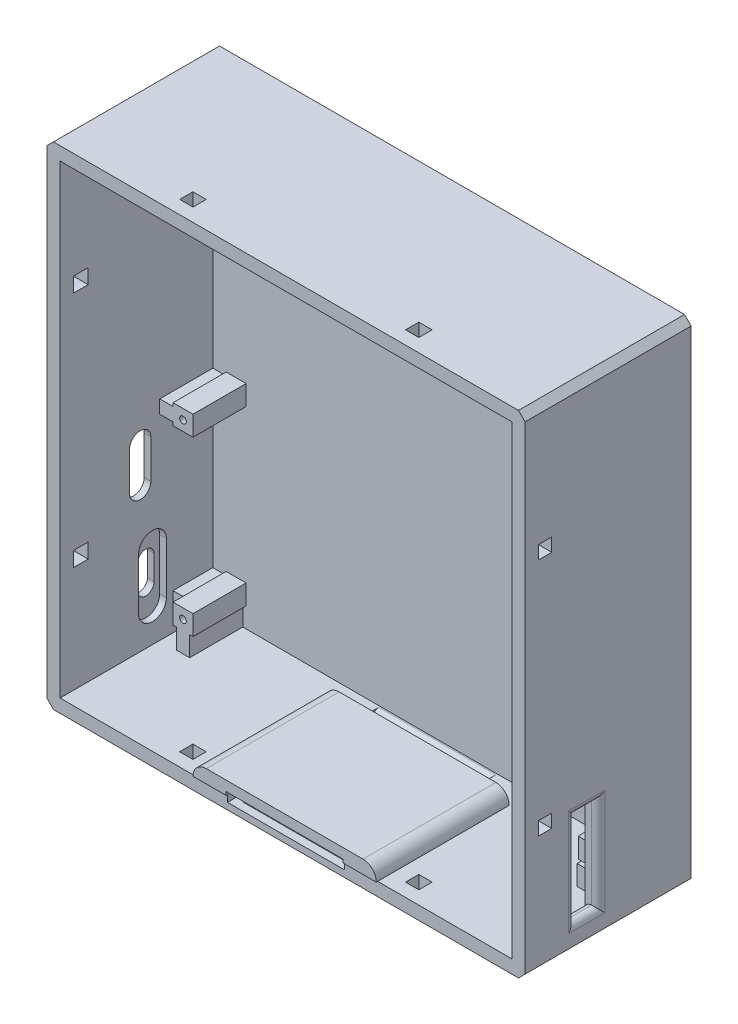
SolidWorks part; units mm, degrees
ref_plane "前视基准面" through (0, 0, 0) normal (0, 0, 1) x (1, 0, 0)
ref_plane "上视基准面" through (0, 0, 0) normal (0, 1, 0) x (1, 0, 0)
ref_plane "右视基准面" through (0, 0, 0) normal (1, 0, 0) x (0, 0, -1)
sketch "草图1" plane through (0, 0, 0) normal (0, 0, 1) x (1, 0, 0)
  line L1 (-21.8087, 48.178) -> (50.1913, 48.178)
  line L2 (-21.8087, 48.178) -> (-21.8087, -25.822)
  line L3 (-21.8087, -25.822) -> (50.1913, -25.822)
  line L4 (50.1913, 48.178) -> (50.1913, -25.822)
  dimension "D1" = 74
  dimension "D2" = 72
extrude "凸台-拉伸1" add sketch "草图1" along normal blind 25
sketch "草图2" plane through (0, 0, 25) normal (0, 0, 1) x (1, 0, 0)
  line L0 (50.1913, 48.178) -> (-21.8087, 48.178) construction
  line L1 (-19.8087, 46.178) -> (48.1913, 46.178)
  line L2 (-19.8087, 46.178) -> (-19.8087, -23.822)
  line L3 (-19.8087, -23.822) -> (48.1913, -23.822)
  line L4 (48.1913, 46.178) -> (48.1913, -23.822)
  line L5 (-21.8087, -25.822) -> (50.1913, -25.822) construction
  line L6 (50.1913, -25.822) -> (50.1913, 48.178) construction
  line L7 (-21.8087, 48.178) -> (-21.8087, -25.822) construction
  dimension "D1" = 2
  dimension "D2" = 2
  dimension "D3" = 2
  dimension "D4" = 2
extrude "切除-拉伸1" cut sketch "草图2" against normal blind 23
sketch "草图3" plane through (0, 46.178, 0) normal (0, -1, 0) x (1, 0, 0)
  line L0 (48.1913, 25) -> (-19.8087, 25) construction
  line L1 (-3.8087, 23) -> (-1.8087, 23)
  line L2 (-3.8087, 23) -> (-3.8087, 21)
  line L3 (-3.8087, 21) -> (-1.8087, 21)
  line L4 (-1.8087, 23) -> (-1.8087, 21)
  line L5 (30.1913, 23) -> (32.1913, 23)
  line L6 (30.1913, 23) -> (30.1913, 21)
  line L7 (30.1913, 21) -> (32.1913, 21)
  line L8 (32.1913, 23) -> (32.1913, 21)
  line L9 (48.1913, 2) -> (48.1913, 25) construction
  line L10 (-19.8087, 2) -> (-19.8087, 25) construction
  dimension "D1" = 2
  dimension "D2" = 2
  dimension "D3" = 2
  dimension "D4" = 16
  dimension "D5" = 16
extrude "切除-拉伸2" cut sketch "草图3" against normal up to next
sketch "草图4" plane through (48.1913, 0, 0) normal (-1, 0, 0) x (0, 0, 1)
  line L1 (23, 30.178) -> (21, 30.178)
  line L2 (23, 30.178) -> (23, 28.178)
  line L3 (23, 28.178) -> (21, 28.178)
  line L4 (21, 30.178) -> (21, 28.178)
  line L5 (23, -5.822) -> (21, -5.822)
  line L6 (23, -5.822) -> (23, -7.822)
  line L7 (23, -7.822) -> (21, -7.822)
  line L8 (21, -5.822) -> (21, -7.822)
  line L10 (25, -23.822) -> (25, 46.178) construction
  line L11 (2, 46.178) -> (25, 46.178) construction
  line L12 (2, -23.822) -> (25, -23.822) construction
  dimension "D1" = 2
  dimension "D2" = 2
  dimension "D3" = 2
  dimension "D4" = 16
  dimension "D5" = 16
sketch "草图5" plane through (0, -23.822, 0) normal (0, 1, 0) x (1, 0, 0)
  line L0 (-19.8087, -25) -> (48.1913, -25) construction
  line L1 (32.1913, -23) -> (30.1913, -23)
  line L2 (32.1913, -23) -> (32.1913, -21)
  line L3 (32.1913, -21) -> (30.1913, -21)
  line L4 (30.1913, -23) -> (30.1913, -21)
  line L5 (-1.8087, -23) -> (-3.8087, -23)
  line L6 (-1.8087, -23) -> (-1.8087, -21)
  line L7 (-1.8087, -21) -> (-3.8087, -21)
  line L8 (-3.8087, -23) -> (-3.8087, -21)
  line L9 (48.1913, -2) -> (48.1913, -25) construction
  line L10 (-19.8087, -2) -> (-19.8087, -25) construction
  dimension "D1" = 2
  dimension "D2" = 2
  dimension "D3" = 16
  dimension "D4" = 16
sketch "草图6" plane through (-19.8087, 0, 0) normal (1, 0, 0) x (0, 0, -1)
  line L0 (-25, 46.178) -> (-25, -23.822) construction
  line L1 (-23, 30.178) -> (-20.7747, 30.178)
  line L2 (-23, 30.178) -> (-23, 27.9527)
  line L3 (-23, 27.9527) -> (-20.7747, 27.9527)
  line L4 (-20.7747, 30.178) -> (-20.7747, 27.9527)
  line L5 (-23, -5.5967) -> (-20.7747, -5.5967)
  line L6 (-23, -5.5967) -> (-23, -7.822)
  line L7 (-23, -7.822) -> (-20.7747, -7.822)
  line L8 (-20.7747, -5.5967) -> (-20.7747, -7.822)
  line L9 (-2, -23.822) -> (-25, -23.822) construction
  line L10 (-2, 46.178) -> (-25, 46.178) construction
  dimension "D1" = 2
  dimension "D2" = 16
  dimension "D3" = 16
extrude "切除-拉伸3" cut sketch "草图4" against normal up to next
extrude "切除-拉伸4" cut sketch "草图5" against normal up to next
extrude "切除-拉伸5" cut sketch "草图6" against normal up to next
sketch "草图7" plane through (0, 0, 2) normal (0, 0, 1) x (1, 0, 0)
  line L1 (-17.8087, -20.822) -> (-14.8087, -20.822)
  line L2 (-17.8087, -20.822) -> (-17.8087, -17.822)
  line L3 (-17.8087, -17.822) -> (-14.8087, -17.822)
  line L4 (-14.8087, -20.822) -> (-14.8087, -17.822)
  line L5 (-17.8087, 5.178) -> (-14.8087, 5.178)
  line L6 (-17.8087, 5.178) -> (-17.8087, 8.178)
  line L7 (-17.8087, 8.178) -> (-14.8087, 8.178)
  line L8 (-14.8087, 5.178) -> (-14.8087, 8.178)
  line L9 (43.1913, -20.822) -> (46.1913, -20.822)
  line L10 (43.1913, -20.822) -> (43.1913, -17.822)
  line L11 (43.1913, -17.822) -> (46.1913, -17.822)
  line L12 (46.1913, -20.822) -> (46.1913, -17.822)
  line L13 (43.1913, 5.178) -> (46.1913, 5.178)
  line L14 (43.1913, 5.178) -> (43.1913, 8.178)
  line L15 (43.1913, 8.178) -> (46.1913, 8.178)
  line L16 (46.1913, 5.178) -> (46.1913, 8.178)
  line L18 (48.1913, -23.822) -> (48.1913, 46.178) construction
  line L19 (-19.8087, 46.178) -> (-19.8087, -23.822) construction
  line L20 (-19.8087, -23.822) -> (48.1913, -23.822) construction
  dimension "D1" = 3
  dimension "D2" = 23
  dimension "D3" = 2
  dimension "D4" = 3
  dimension "D5" = 2
extrude "凸台-拉伸2" add sketch "草图7" along normal blind 8
sketch "草图10" plane through (0, 0, 10) normal (0, 0, 1) x (1, 0, 0)
  line L0 (-17.8087, -17.822) -> (-14.8087, -20.822) construction
  line L1 (-14.8087, -20.822) -> (-14.8087, -17.822) construction
  line L2 (-14.8087, -17.822) -> (-17.8087, -20.822) construction
  line L3 (43.1913, 8.178) -> (46.1913, 5.178) construction
  line L4 (46.1913, 5.178) -> (46.1913, 8.178) construction
  line L5 (46.1913, 8.178) -> (43.1913, 5.178) construction
  circle A0 centre (44.6913, 6.678) radius 0.5
  circle A1 centre (44.6913, -19.322) radius 0.5
  circle A2 centre (-16.3087, -19.322) radius 0.5
  circle A3 centre (-16.3087, 6.678) radius 0.5
  point P17 (-16.3087, -19.322)
  point P26 (44.6913, 6.678)
  dimension "D1" = 1
extrude "切除-拉伸6" cut sketch "草图10" against normal blind 3
sketch "草图12" plane through (-17.8087, 0, 0) normal (-1, 0, 0) x (0, 0, 1)
  line L1 (2, -18.322) -> (8, -18.322)
  line L2 (2, -18.322) -> (2, -20.322)
  line L3 (2, -20.322) -> (8, -20.322)
  line L4 (8, -18.322) -> (8, -20.322)
  line L5 (2, -17.822) -> (2, -20.822) construction
  line L6 (10, -17.822) -> (10, -20.822) construction
  line L7 (2, 7.678) -> (10, 7.678)
  line L8 (2, 7.678) -> (2, 5.678)
  line L9 (2, 5.678) -> (10, 5.678)
  line L10 (10, 7.678) -> (10, 5.678)
  line L11 (10, 5.178) -> (2, 5.178) construction
  line L12 (10, 8.178) -> (10, 5.178) construction
  line L13 (2, 8.178) -> (2, 5.178) construction
  line L14 (10, -20.822) -> (2, -20.822) construction
  dimension "D1" = 0.5
  dimension "D2" = 2
  dimension "D3" = 2
  dimension "D4" = 0.5
  dimension "D5" = 2
extrude "凸台-拉伸3" add sketch "草图12" along normal up to next
sketch "草图13" plane through (46.1913, 0, 0) normal (1, 0, 0) x (0, 0, -1)
  line L1 (-10, 7.678) -> (-2, 7.678)
  line L2 (-10, 7.678) -> (-10, 5.678)
  line L3 (-10, 5.678) -> (-2, 5.678)
  line L4 (-2, 7.678) -> (-2, 5.678)
  line L5 (-10, 5.178) -> (-10, 8.178) construction
  line L6 (-2, 5.178) -> (-2, 8.178) construction
  line L7 (-10, 5.178) -> (-2, 5.178) construction
  line L8 (-10, -20.822) -> (-10, -17.822) construction
  line L9 (-10, -18.322) -> (-2, -18.322)
  line L10 (-10, -18.322) -> (-10, -20.322)
  line L11 (-10, -20.322) -> (-2, -20.322)
  line L12 (-2, -18.322) -> (-2, -20.322)
  line L13 (-2, -20.822) -> (-2, -17.822) construction
  line L14 (-10, -20.822) -> (-2, -20.822) construction
  point P20 (-6, -20.822)
  dimension "D1" = 2
  dimension "D2" = 0.5
  dimension "D3" = 2
  dimension "D4" = 0.5
extrude "凸台-拉伸4" add sketch "草图13" along normal up to next
sketch "草图14" plane through (0, -20.822, 0) normal (0, -1, 0) x (1, 0, 0)
  line L0 (-17.8087, 10) -> (-14.8087, 10) construction
  line L1 (-17.3087, 10) -> (-15.3087, 10)
  line L2 (-17.3087, 10) -> (-17.3087, 2)
  line L3 (-17.3087, 2) -> (-15.3087, 2)
  line L4 (-15.3087, 10) -> (-15.3087, 2)
  line L5 (43.6913, 10.6583) -> (45.6913, 10.6583)
  line L6 (43.6913, 10.6583) -> (43.6913, 4.0576)
  line L7 (43.6913, 4.0576) -> (45.6913, 4.0576)
  line L8 (45.6913, 10.6583) -> (45.6913, 4.0576)
  line L9 (-17.8087, 2) -> (-14.8087, 2) construction
  line L11 (-17.8087, 10) -> (-17.8087, 2) construction
  line L13 (43.1913, 10) -> (43.1913, 2) construction
  dimension "D1" = 2
  dimension "D2" = 2
  dimension "D3" = 0.5
  dimension "D4" = 0.5
extrude "凸台-拉伸5" add sketch "草图14" along normal up to next
sketch "草图15" plane through (-21.8087, 0, 0) normal (-1, 0, 0) x (0, 0, 1)
  line L0 (12.94, 3.798) -> (12.94, -2.402) construction
  line L1 (16.54, 3.798) -> (16.54, -2.402)
  line L2 (9.34, 3.798) -> (9.34, -2.402)
  line L4 (25, -25.822) -> (0, -25.822) construction
  line L5 (0, 48.178) -> (0, -25.822) construction
  arc A0 (16.54, 3.798) -> (9.34, 3.798) centre (12.94, 3.798) ccw
  arc A1 (9.34, -2.402) -> (16.54, -2.402) centre (12.94, -2.402) ccw
  point P0 (12.94, -6.002)
  point P3 (12.94, 0.698)
  point P8 (9.34, 0.698)
  dimension "D3" = 19.82
  dimension "D1" = 6.2
  dimension "D2" = 7.2
  dimension "D4" = 9.34
extrude "切除-拉伸8" cut sketch "草图15" against normal blind 1
sketch "草图18" plane through (-20.8087, 0, 0) normal (-1, 0, 0) x (0, 0, 1)
  line L0 (12.94, 3.398) -> (12.94, -2.402) construction
  line L3 (14.54, 3.398) -> (14.54, -2.402)
  line L4 (11.34, 3.398) -> (11.34, -2.402)
  line L5 (16.54, -2.402) -> (16.54, 3.798) construction
  arc A2 (9.34, -2.402) -> (16.54, -2.402) centre (12.94, -2.402) ccw construction
  arc A3 (14.54, 3.398) -> (11.34, 3.398) centre (12.94, 3.398) ccw
  arc A4 (11.34, -2.402) -> (14.54, -2.402) centre (12.94, -2.402) ccw
  point P2 (12.94, 0.498)
  point P7 (12.94, 4.998)
  point P8 (12.94, -4.002)
  point P12 (12.94, -6.002)
  dimension "D1" = 3.2
  dimension "D2" = 9
  dimension "D3" = 2
  dimension "D4" = 2
extrude "切除-拉伸9" cut sketch "草图18" against normal blind 1
sketch "草图19" plane through (-19.8087, 0, 0) normal (1, 0, 0) x (0, 0, -1)
  line L0 (-11.1, -11.022) -> (-11.1, -18.722) construction
  line L1 (-9, -11.022) -> (-9, -18.722)
  line L2 (-13.2, -11.022) -> (-13.2, -18.722)
  line L3 (-2, 5.678) -> (-2, -18.322) construction
  line L4 (-2, -23.822) -> (-25, -23.822) construction
  arc A0 (-9, -11.022) -> (-13.2, -11.022) centre (-11.1, -11.022) ccw
  arc A1 (-13.2, -18.722) -> (-9, -18.722) centre (-11.1, -18.722) ccw
  point P2 (-11.1, -14.872)
  point P9 (-11.1, -20.822)
  dimension "D1" = 7.7
  dimension "D2" = 4.2
  dimension "D3" = 7
  dimension "D4" = 3
extrude "切除-拉伸10" cut sketch "草图19" against normal blind 1 contours L1 A1 L2 A0
sketch "草图20" plane through (-20.8087, 0, 0) normal (1, 0, 0) x (0, 0, -1)
  line L0 (-12.35, -16.722) -> (-12.35, -13.2168)
  line L1 (-9.85, -13.0402) -> (-9.85, -16.722)
  line L3 (-9, -11.022) -> (-9, -18.722) construction
  arc A0 (-9.85, -13.0402) -> (-12.35, -13.2168) centre (-11.1005, -13.122) ccw
  arc A1 (-12.35, -16.722) -> (-9.85, -16.722) centre (-11.1, -16.722) ccw
  arc A3 (-13.2, -18.722) -> (-9, -18.722) centre (-11.1, -18.722) ccw construction
  dimension "D4" = 0.85
  dimension "D5" = 1.25
  dimension "D6" = 1.2531
  dimension "D1" = 2.5
  dimension "D2" = 3.6
  dimension "D3" = 2
extrude "切除-拉伸11" cut sketch "草图20" against normal blind 1
sketch "草图21" plane through (50.1913, 0, 0) normal (1, 0, 0) x (0, 0, -1)
  line L0 (0, -25.822) -> (0, 48.178) construction
  line L1 (-17.5, -21.822) -> (-14, -21.822)
  line L2 (-17.5, -21.822) -> (-17.5, -7.822)
  line L3 (-17.5, -7.822) -> (-14, -7.822)
  line L4 (-14, -21.822) -> (-14, -7.822)
  line L5 (-25, -25.822) -> (0, -25.822) construction
  dimension "D1" = 17.5
  dimension "D2" = 3.5
  dimension "D3" = 4
  dimension "D4" = 14
extrude "切除-拉伸12" cut sketch "草图21" against normal up to next
sketch "草图22" plane through (0, -23.822, 0) normal (0, 1, 0) x (1, 0, 0)
  line L0 (48.1913, -2) -> (48.1913, -25) construction
  line L1 (5.3913, -25) -> (22.9913, -25)
  line L2 (5.3913, -25) -> (5.3913, -3.2)
  line L3 (5.3913, -3.2) -> (22.9913, -3.2)
  line L4 (22.9913, -25) -> (22.9913, -3.2)
  line L6 (-19.8087, -25) -> (48.1913, -25) construction
  dimension "D1" = 42.8
  dimension "D2" = 17.6
  dimension "D3" = 21.8
extrude "切除-拉伸13" cut sketch "草图22" against normal blind 1 contours L2 L1 L4 L3
sketch "草图24" plane through (0, -24.822, 0) normal (0, 1, 0) x (1, 0, 0)
  line L0 (5.3913, -25) -> (5.3913, -3.2) construction
  line L1 (6.5913, -23.8) -> (21.7913, -23.8)
  line L2 (6.5913, -23.8) -> (6.5913, -8.6)
  line L3 (6.5913, -8.6) -> (21.7913, -8.6)
  line L4 (21.7913, -23.8) -> (21.7913, -8.6)
  line L6 (5.3913, -25) -> (22.9913, -25) construction
  dimension "D1" = 15.2
  dimension "D2" = 15.2
  dimension "D3" = 1.2
  dimension "D4" = 1.2
extrude "切除-拉伸14" cut sketch "草图24" against normal blind 1
sketch "草图27" plane through (0, -23.822, 0) normal (0, 1, 0) x (1, 0, 0)
  line L0 (5.3913, -25) -> (5.3913, -3.2) construction
  line L1 (0.3913, -25.2) -> (27.9913, -25.2)
  line L2 (0.3913, -25.2) -> (0.3913, -5.2)
  line L3 (0.3913, -5.2) -> (27.9913, -5.2)
  line L4 (27.9913, -25.2) -> (27.9913, -5.2)
  line L5 (22.9913, -25) -> (22.9913, -3.2) construction
  line L6 (5.3913, -3.2) -> (22.9913, -3.2) construction
  dimension "D1" = 5
  dimension "D2" = 5
  dimension "D3" = 20
  dimension "D4" = 2
extrude "凸台-拉伸6" add sketch "草图27" along normal blind 2 contours L2 L1 L4 L3
sketch "草图28" plane through (0, 0, 25.2) normal (0, 0, 1) x (1, 0, 0)
  line L0 (0.3913, -23.822) -> (27.9913, -23.822) construction
  line L1 (5.3889, -23.822) -> (22.9913, -23.822)
  line L2 (5.3889, -23.822) -> (5.3889, -23.322)
  line L3 (5.3889, -23.322) -> (22.9913, -23.322)
  line L4 (22.9913, -23.822) -> (22.9913, -23.322)
  line L5 (22.9913, -24.822) -> (22.9913, -23.822) construction
  dimension "D1" = 0.5
extrude "切除-拉伸16" cut sketch "草图28" against normal up to next contours L2 L1 L4 L3
fillet "圆角1" radius 1 1 edges at (14.1913, -23.822, 3.2)
fillet "圆角2" radius 2 2 edges at (0.3913, -21.822, 15.2) (27.9913, -21.822, 15.2)
chamfer "倒角1" distance 1 angle 45 4 edges at (50.1913, -25.822, 12.5) (50.1913, 48.178, 12.5) (-21.8087, -25.822, 12.5) (-21.8087, 48.178, 12.5)
fillet "圆角3" radius 1 2 edges at (48.1913, -21.822, 15.75) (48.1913, -7.822, 15.75)
fillet "圆角4" radius 1 4 edges at (50.1913, -14.822, 17.5) (50.1913, -14.822, 14) (50.1913, -21.822, 15.75) (50.1913, -7.822, 15.75)
chamfer "倒角3" distance 0.5 angle 45 4 edges at (6.5913, -25.822, 16.2) (14.1913, -25.822, 8.6) (21.7913, -25.822, 16.2) (14.1913, -25.822, 23.8)
